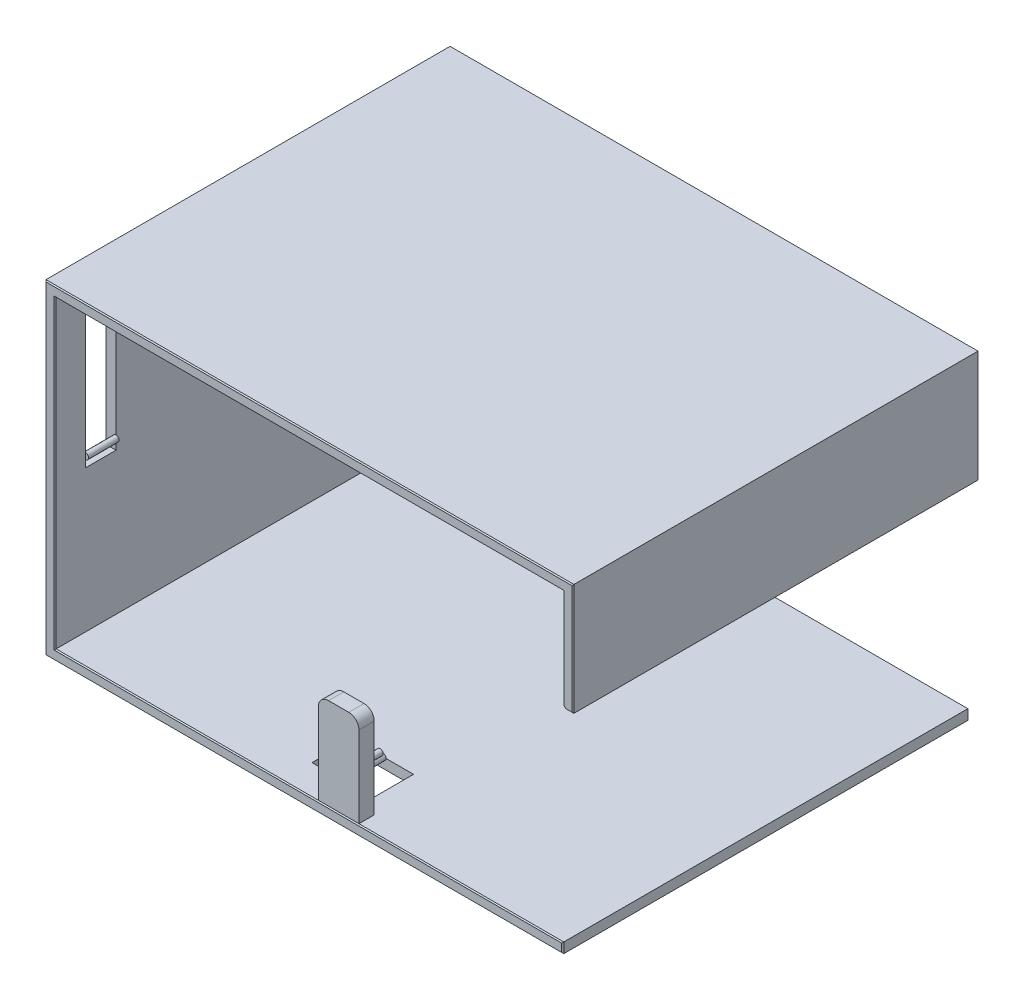
SolidWorks part; units mm, degrees
note: The reader was unsure of these and kept them because the rebuilt part matched: shared geometry of "Sketch5<2>", "Sketch7<2>", "Sketch13<2>".
ref_plane "Front Plane" through (0, 0, 0) normal (0, 0, 1) x (1, 0, 0)
ref_plane "Top Plane" through (0, 0, 0) normal (0, 1, 0) x (1, 0, 0)
ref_plane "Right Plane" through (0, 0, 0) normal (1, 0, 0) x (0, 0, -1)
sketch "Sketch1" plane through (0, 0, 0) normal (0, 0, 1) x (1, 0, 0)
  line L1 (2500, -1500) -> (-2500, -1500)
  line L3 (2500, 1500) -> (-2500, 1500)
  line L4 (-2500, -1500) -> (-2500, 700)
  line L5 (2500, 1500) -> (2500, 500)
  line L6 (2500, 500) -> (2600, 500)
  line L7 (2600, 500) -> (2600, 1600)
  line L8 (2600, 1600) -> (-2600, 1600)
  line L9 (-2600, 1600) -> (-2600, -1600)
  line L10 (-2600, -1600) -> (2500, -1600)
  line L11 (2500, -1600) -> (2500, -1500)
  line L15 (-2500, 700) -> (-2500, 1500)
  point P0 (0, 0)
  point P9 (-2500, 0)
  point P10 (0, 1500)
  point P12 (2500, 500)
  dimension "D1" = 3000
  dimension "D2" = 5000
  dimension "D4" = 1500
  dimension "D6" = 1000
  dimension "D9" = 100
  dimension "D7" = 100
  dimension "D8" = 100
  dimension "D10" = 100
extrude "Boss-Extrude1" add sketch "Sketch1" along normal mid plane 4000 contours L4 L15 L3 L5 L6 L7 L8 L9 L10 L11 L1
sketch "Sketch4" plane through (0, -1500, 0) normal (0, 1, 0) x (1, 0, 0)
  line L0 (1506.4763, 0) -> (-1944.2474, 0) construction
  line L1 (-270, -1300) -> (330, -1300)
  line L2 (-270, -1300) -> (-270, -1700)
  line L3 (-270, -1700) -> (330, -1700)
  line L4 (330, -1300) -> (330, -1700)
  line L5 (-270, -1300) -> (330, -1700) construction
  line L6 (-270, -1700) -> (330, -1300) construction
  line L7 (-270, 1700) -> (330, 1300) construction
  line L8 (-270, 1300) -> (330, 1700) construction
  line L9 (330, 1300) -> (330, 1700)
  line L10 (-270, 1700) -> (330, 1700)
  line L11 (-270, 1300) -> (-270, 1700)
  line L12 (-270, 1300) -> (330, 1300)
  point P0 (30, -1500)
  point P12 (30, 1500)
  dimension "D1" = 400
  dimension "D2" = 1500
  dimension "D4" = 600
  dimension "D3" = 30
extrude "Cut-Extrude1" cut sketch "Sketch4" against normal through all
sketch "Sketch5" plane through (0, 0, 0) normal (0, 0, 1) x (1, 0, 0)
  line L0 (2500, -1500) -> (-2500, -1500) construction
  circle A0 centre (30, -1500) radius 30
  dimension "D1" = 60
  dimension "D2" = 30
extrude "Boss-Extrude5" add sketch "Sketch5" along normal up to surface (400 mm away) from surface at 1300 up to face at (30, -1550, 1700) starting at face at (30, -1550, 1300)
extrude "Boss-Extrude6" add sketch "Sketch5<2>" against normal up to surface (400 mm away) from surface at -1300 up to face at (30, -1550, -1700) starting at face at (30, -1550, -1300)
sketch "Sketch5<2>" plane through (0, 0, 0) normal (0, 0, 1) x (1, 0, 0) same geometry as "Sketch5"
sketch "Sketch6" plane through (-2500, 0, 0) normal (1, 0, 0) x (0, 0, -1)
  line L0 (0, 782.2645) -> (0, -782.2645) construction
  line L1 (-1700, 1500) -> (-1400, 1500)
  line L2 (-1700, 1500) -> (-1700, -100)
  line L3 (-1700, -100) -> (-1400, -100)
  line L4 (-1400, 1500) -> (-1400, -100)
  line L5 (-1700, 1500) -> (-1400, -100) construction
  line L6 (-1700, -100) -> (-1400, 1500) construction
  line L7 (1700, -100) -> (1400, 1500) construction
  line L8 (1700, 1500) -> (1400, -100) construction
  line L9 (1400, 1500) -> (1400, -100)
  line L10 (1700, -100) -> (1400, -100)
  line L11 (1700, 1500) -> (1700, -100)
  line L12 (1700, 1500) -> (1400, 1500)
  line L15 (-2000, -1500) -> (-2000, 1500) construction
  line L16 (-2000, 1500) -> (2000, 1500) construction
  point P0 (-1550, 700)
  point P12 (1550, 700)
  dimension "D1" = 300
  dimension "D2" = 450
  dimension "D3" = 100
extrude "Cut-Extrude2" cut sketch "Sketch6" against normal through all
sketch "Sketch7" plane through (0, 0, 0) normal (0, 0, 1) x (1, 0, 0)
  circle A0 centre (-2500, 0) radius 30
  dimension "D1" = 60
  dimension "D2" = 2500
extrude "Boss-Extrude7" add sketch "Sketch7" against normal up to surface (300 mm away) from surface at -1400 up to face at (-2550, 700, -1700) starting at face at (-2550, 700, -1400)
extrude "Boss-Extrude8" add sketch "Sketch7<2>" along normal up to surface (300 mm away) from surface at 1400 up to face at (-2550, 700, 1700) starting at face at (-2550, 700, 1400)
sketch "Sketch7<2>" plane through (0, 0, 0) normal (0, 0, 1) x (1, 0, 0) same geometry as "Sketch7"
sketch "Sketch10" plane through (0, 0, 0) normal (0, 0, 1) x (1, 0, 0)
  line L0 (-2500, -1500) -> (-2500, 1500) construction
  line L1 (-2500, 740) -> (-1000, 740)
  line L2 (-2500, 740) -> (-2500, 640)
  line L3 (-2500, 640) -> (-1000, 640)
  line L4 (-1000, 740) -> (-1000, 640)
  line L5 (-2500, 740) -> (-1000, 640) construction
  line L6 (-2500, 640) -> (-1000, 740) construction
  line L7 (2500, -1500) -> (-2500, -1500) construction
  point P0 (-1750, 690)
  dimension "D1" = 2240
  dimension "D2" = 100
  dimension "D3" = 1500
extrude "Boss-Extrude9" add sketch "Sketch10" along normal mid plane 2000
chamfer "Chamfer1" distance 10 angle 45 30 edges at (-2500, 640, 0) (-1750, 640, 1000) (-1000, 640, 0) (-1750, 640, -1000) (-2500, 690, 1000) (-2500, 690, -1000) (-1000, 740, 0) (-1750, 740, 1000) (-2500, 740, 0) (-1750, 740, -1000) (-2500, 0, -2000) (0, 1500, -2000) (2500, 1000, -2000) (2550, 500, -2000) (2600, 1050, -2000) (0, 1600, -2000) (-2600, 0, -2000) (-50, -1600, -2000) (2500, -1550, -2000) (0, -1500, -2000) (2500, -1550, 2000) (-50, -1600, 2000) (-2600, 0, 2000) (0, 1600, 2000) (2600, 1050, 2000) (2550, 500, 2000) (2500, 1000, 2000) (0, 1500, 2000) (-2500, 0, 2000) (0, -1500, 2000)
sketch "Sketch12" plane through (0, -1500, 0) normal (0, 1, 0) x (1, 0, 0)
  line L0 (-2500, -1990) -> (2500, -1990) construction
  line L1 (82.5, -1840) -> (482.5, -1840)
  line L2 (82.5, -1840) -> (82.5, -1990)
  line L3 (82.5, -1990) -> (482.5, -1990)
  line L4 (482.5, -1840) -> (482.5, -1990)
  line L5 (82.5, -1840) -> (482.5, -1990) construction
  line L6 (82.5, -1990) -> (482.5, -1840) construction
  line L7 (1650.9433, 0) -> (-2231.1334, 0) construction
  line L8 (82.5, 1990) -> (482.5, 1840) construction
  line L9 (82.5, 1840) -> (482.5, 1990) construction
  line L10 (482.5, 1840) -> (482.5, 1990)
  line L11 (82.5, 1990) -> (482.5, 1990)
  line L12 (82.5, 1840) -> (82.5, 1990)
  line L13 (82.5, 1840) -> (482.5, 1840)
  point P0 (282.5, -1915)
  point P14 (282.5, 1915)
  dimension "D1" = 150
  dimension "D2" = 400
  dimension "D3" = 282.5
extrude "Boss-Extrude10" add sketch "Sketch12" along normal blind 900
fillet "Fillet4" radius 100 4 edges at (482.5, -600, 1915) (82.5, -600, 1915) (82.5, -600, -1915) (482.5, -600, -1915)
sketch "Sketch13" plane through (0, 0, 0) normal (0, 0, 1) x (1, 0, 0)
  line L0 (482.5, -1500) -> (2500, -1500) construction
  circle A0 centre (276.56, -1200) radius 30
  dimension "D1" = 60
  dimension "D2" = 300
  dimension "D3" = 276.56
extrude "Boss-Extrude11" add sketch "Sketch13" along normal up to surface (265 mm away) from offset 1575 up to face at (282.5, -926.4298, 1840)
extrude "Boss-Extrude12" add sketch "Sketch13<2>" against normal up to surface (265 mm away) from offset 1575 up to face at (282.5, -926.4298, -1840) offset against normal yes
sketch "Sketch13<2>" plane through (0, 0, 0) normal (0, 0, 1) x (1, 0, 0) same geometry as "Sketch13"
chamfer "Chamfer4" distance 40 angle 45 1 edges at (2500, 500, 0)
equation "\"Thick\"= 100"
equation "\"D9@Sketch1\"=\"Thick\""
equation "\"D7@Sketch1\"=\"Thick\""
equation "\"D8@Sketch1\"=\"Thick\""
equation "\"D10@Sketch1\"=\"Thick\""
equation "\"D\"= 60"
equation "\"Actoator Location\"= 30"
equation "\"D1@Sketch7\"=\"D\""
equation "\"D2@Sketch10\"=\"Thick\""
equation "\"D1@Sketch13\"=\"D\""
equation "\"Actuator b Location\"= 276.56"
equation "\"D3@Sketch13\"=\"Actuator b Location\""
equation "\"D2@Sketch5\"=\"Actoator Location\""
equation "\"D3@Sketch4\"=\"Actoator Location\""
